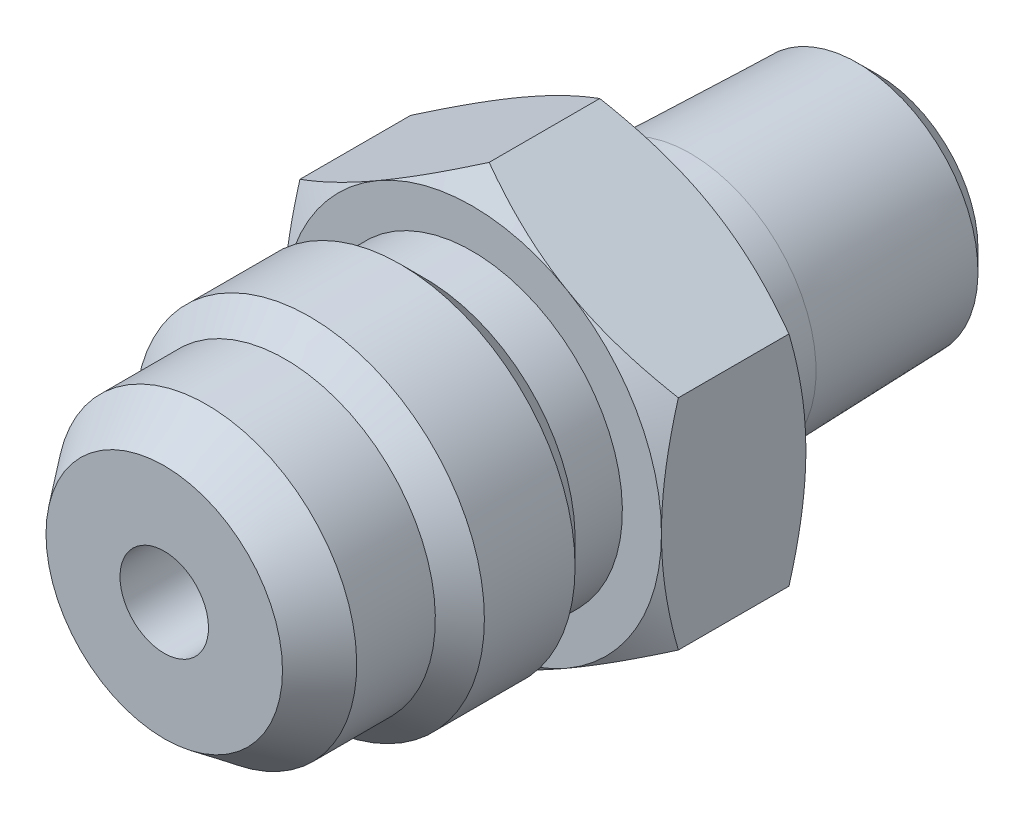
SolidWorks part; units mm, degrees
ref_plane "Front" through (0, 0, 0) normal (0, 0, 1) x (1, 0, 0)
ref_plane "Top" through (0, 0, 0) normal (0, 1, 0) x (1, 0, 0)
ref_plane "Right" through (0, 0, 0) normal (1, 0, 0) x (0, 0, -1)
sketch "Sketch1" plane through (0, 0, 0) normal (1, 0, 0) x (0, 0, -1)
  line L0 (-19.4469, 0) -> (19.4469, 0) construction
  line L1 (-19.4469, 2.413) -> (-19.4469, 6.4481)
  line L2 (-19.4469, 6.4481) -> (-17.1383, 8.1877)
  line L3 (-17.1383, 8.1877) -> (-12.8508, 8.1877)
  line L4 (-12.8508, 8.1877) -> (-11.5135, 9.525)
  line L5 (-11.5135, 9.525) -> (-6.5681, 9.525)
  line L6 (-6.5681, 9.525) -> (-5.2308, 8.1877)
  line L7 (-5.2308, 8.1877) -> (-2.6511, 8.1877)
  line L8 (-19.4469, 6.4481) -> (-18.7873, 6.4481) construction
  line L9 (-18.7873, 6.4481) -> (-18.1277, 6.4481) construction
  line L10 (-2.6511, 8.1877) -> (-2.6511, 10.3187)
  line L11 (-2.6511, 10.3187) -> (5.2229, 10.3187)
  line L12 (5.2229, 10.3187) -> (5.2229, 6.858)
  line L13 (5.2229, 6.858) -> (9.2412, 6.858)
  line L14 (9.2412, 6.858) -> (18.3545, 6.5743)
  line L15 (19.4469, 5.4819) -> (19.4469, 2.413)
  line L16 (19.4469, 2.413) -> (-19.4469, 2.413)
  line L17 (-17.1383, 8.1877) -> (-19.4469, 8.1877) construction
  line L18 (-19.4469, 8.1877) -> (-19.4469, 6.4481) construction
  line L19 (-11.5135, 9.525) -> (-12.8508, 9.525) construction
  line L20 (-12.8508, 9.525) -> (-12.8508, 8.1877) construction
  line L21 (-6.5681, 9.525) -> (-5.2308, 9.525) construction
  line L22 (-5.2308, 9.525) -> (-5.2308, 8.1877) construction
  line L23 (9.2412, 6.858) -> (19.4469, 6.858) construction
  line L24 (18.3545, 6.5743) -> (19.4469, 5.4819)
  line L25 (18.3545, 6.5743) -> (19.4469, 6.5402) construction
  line L26 (19.4469, 5.4819) -> (19.4469, 6.5402) construction
  line L27 (19.4469, 6.5402) -> (19.4469, 6.858) construction
  line L28 (19.4469, 6.5402) -> (19.976, 5.6237) construction
  line L29 (19.976, 5.6237) -> (20.1524, 5.6237) construction
  line L30 (20.1524, 5.6237) -> (20.7549, 6.6672) construction
  line L31 (20.7549, 6.6672) -> (19.3736, 6.6672) construction
  line L32 (19.3736, 6.6672) -> (19.4469, 6.5402) construction
  line L33 (19.7115, 6.082) -> (20.417, 6.082) construction
  line L34 (20.0642, 6.082) -> (20.0642, 5.6237) construction
  line L35 (20.0642, 5.8528) -> (21.4753, 5.8528) construction
  line L36 (-12.8508, 9.525) -> (-19.4469, 9.525) construction
  line L37 (-19.4469, 9.525) -> (-19.4469, 8.1877) construction
  line L38 (-19.4469, 9.525) -> (-20.0422, 8.4939) construction
  line L39 (-20.0422, 8.4939) -> (-20.2406, 8.4939) construction
  line L40 (-20.2406, 8.4939) -> (-20.9093, 9.652) construction
  line L41 (-20.9093, 9.652) -> (-19.3736, 9.652) construction
  line L42 (-19.3736, 9.652) -> (-19.4469, 9.525) construction
  line L43 (-19.7445, 9.0094) -> (-20.5383, 9.0094) construction
  line L44 (-20.1414, 9.0094) -> (-20.1414, 8.4939) construction
  line L45 (-20.1414, 8.7517) -> (-21.7289, 8.7517) construction
  line L46 (-18.1277, 6.4481) -> (-17.4681, 6.4481) construction
  line L47 (-17.4681, 6.4481) -> (-16.8085, 6.4481) construction
  line L48 (-16.8085, 6.4481) -> (-16.1488, 6.4481) construction
  line L49 (-16.1488, 6.4481) -> (-15.4892, 6.4481) construction
  line L50 (-15.4892, 6.4481) -> (-14.8296, 6.4481) construction
  line L51 (-14.8296, 6.4481) -> (-14.17, 6.4481) construction
  line L52 (-14.17, 6.4481) -> (-13.5104, 6.4481) construction
  line L53 (-13.5104, 6.4481) -> (-12.8508, 6.4481) construction
  line L54 (-12.8508, 8.1877) -> (-12.8508, 6.4481) construction
  line L55 (-17.1383, 8.1877) -> (-17.1383, 6.4481) construction
  dimension "D1" = 37
  dimension "D3" = 45
  dimension "D4" = 1.783
  dimension "D2" = 0.127
  dimension "D5" = 60
  dimension "D6" = 0.1764
  dimension "D7" = 0.7056
  dimension "D8" = 1.0583
  dimension "D9" = 0.127
  dimension "D10" = 60
  dimension "D11" = 0.1984
  dimension "D12" = 0.7937
  dimension "D13" = 2.5797
revolve "Revolve1" add sketch "Sketch1" angle 360 about L0
sketch "Sketch2" plane through (0, 0, 2.6511) normal (0, 0, 1) x (1, 0, 0)
  line L1 (0, 11.9151) -> (-10.3188, 5.9575)
  line L2 (-10.3188, 5.9575) -> (-10.3188, -5.9575)
  line L3 (-10.3188, -5.9575) -> (0, -11.9151)
  line L4 (0, -11.9151) -> (10.3188, -5.9575)
  line L5 (10.3188, -5.9575) -> (10.3188, 5.9575)
  line L6 (10.3188, 5.9575) -> (0, 11.9151)
  circle A0 centre (0, 0) radius 10.3187 construction
  circle A1 centre (0, 0) radius 10.3187 construction
  circle A2 centre (0, 0) radius 10.1917
  dimension "D1" = 0.127
extrude "Boss-Extrude1" add sketch "Sketch2" against normal up to surface (7.874 mm away) up to face at (0, -10.3187, -5.2229)
sketch "Sketch3" plane through (0, 0, 0) normal (1, 0, 0) x (0, 0, -1)
  line L0 (-19.4469, 0) -> (19.4469, 0) construction
  line L1 (1.2859, 10.3187) -> (1.2859, 0) construction
  line L2 (-2.6511, 10.3187) -> (5.2229, 10.3187) construction
  line L3 (-2.6511, 10.3187) -> (-2.6511, 11.9151)
  line L4 (-2.6511, 11.9151) -> (-1.7295, 11.9151)
  line L5 (5.2229, 11.9151) -> (-2.6511, 11.9151) construction
  line L6 (-1.7295, 11.9151) -> (-2.6511, 10.3187)
  line L7 (4.3012, 11.9151) -> (5.2229, 10.3187)
  line L8 (5.2229, 11.9151) -> (4.3012, 11.9151)
  line L9 (5.2229, 10.3187) -> (5.2229, 11.9151)
  dimension "D1" = 30
revolve "Cut-Revolve1" cut sketch "Sketch3" angle 360 about L0
sketch "Sketch4" plane through (0, 0, 19.4469) normal (0, 0, 1) x (1, 0, 0)
  circle A0 centre (0, 0) radius 9.525 construction
  circle A1 centre (0, 0) radius 9.525
curve "Helix/Spiral1" pitch 1.5875 height 16.7957 turns 10.58
sketch "Sketch5" [suppressed] plane through (0, 0, 0) normal (1, 0, 0) x (0, 0, -1)
  line L0 (-19.3736, 9.652) -> (-20.0422, 8.4939)
  line L1 (-20.0422, 8.4939) -> (-20.2406, 8.4939)
  line L2 (-20.2406, 8.4939) -> (-20.9093, 9.652)
  line L3 (-20.9093, 9.652) -> (-19.3736, 9.652)
sweep "Sweep1" [suppressed] add profiles "Sketch5" path "Helix/Spiral1"
sketch "Sketch6" [suppressed] plane through (0, 0, -19.4469) normal (0, 0, -1) x (-1, 0, 0)
  circle A0 centre (0, 0) radius 6.5402
curve "Helix/Spiral2" [suppressed]
sketch "Sketch7" [suppressed] plane through (0, 0, 0) normal (1, 0, 0) x (0, 0, -1)
  line L0 (19.3736, 6.6672) -> (19.976, 5.6237)
  line L1 (19.976, 5.6237) -> (20.1524, 5.6237)
  line L2 (20.1524, 5.6237) -> (20.7549, 6.6672)
  line L3 (20.7549, 6.6672) -> (19.3736, 6.6672)
sweep "Sweep2" [suppressed] add profiles "Sketch7" path "Helix/Spiral2"
sketch "Sketch8" [suppressed] plane through (0, 0, 0) normal (1, 0, 0) x (0, 0, -1)
  line L0 (-19.4469, 0) -> (19.4469, 0) construction
  line L1 (-5.2308, -11.9151) -> (9.2412, -11.9151)
  line L2 (-5.2308, -11.9151) -> (-5.2308, 11.9151)
  line L3 (-5.2308, 11.9151) -> (9.2412, 11.9151)
  line L4 (9.2412, -11.9151) -> (9.2412, 11.9151)
  line L5 (-5.2308, -11.9151) -> (9.2412, 11.9151) construction
  line L6 (-5.2308, 11.9151) -> (9.2412, -11.9151) construction
  line L7 (4.3012, 11.9151) -> (-1.7295, 11.9151) construction
  point P0 (2.0052, 0)
extrude "Cut-Extrude1" [suppressed] cut sketch "Sketch8" against normal through all both and the other way through all
combine bodies "Combine1" [suppressed] operation type add bodies to combine 111 114 115
other "CPoint1" parameters "Diameter"=12.7, "StubLength"=38.1
ref_axis "Axis1" through (0, 0, 29.4469) along (0, 0, -1)
equation "\"D6@Sketch1\"=\"ThreadPitch2@Sketch1\"*.125"
equation "\"D7@Sketch1\"=\"ThreadPitch2@Sketch1\"*.5"
equation "\"D8@Sketch1\"=\"ThreadPitch2@Sketch1\"*.75"
equation "\"D11@Sketch1\"=\"ThreadPitch1@Sketch1\"*.125"
equation "\"D12@Sketch1\"=\"ThreadPitch1@Sketch1\"*.5"
equation "\"D4@Helix/Spiral1\"=\"ThreadPitch1@Sketch1\""
equation "\"D3@Helix/Spiral1\"=\"Length@Sketch1\"-(\"HexWidth@Sketch1\"+\"SideLength2@Sketch1\")"
equation "\"D4@Helix/Spiral2\"=\"ThreadPitch2@Sketch1\""
equation "\"D3@Helix/Spiral2\"=\"ThreadFTE2@Sketch1\"+\"ThreadPitch2@Sketch1\""
equation "\"D13@Sketch1\"=\"ThreadPitch1@Sketch1\"*1.625"
